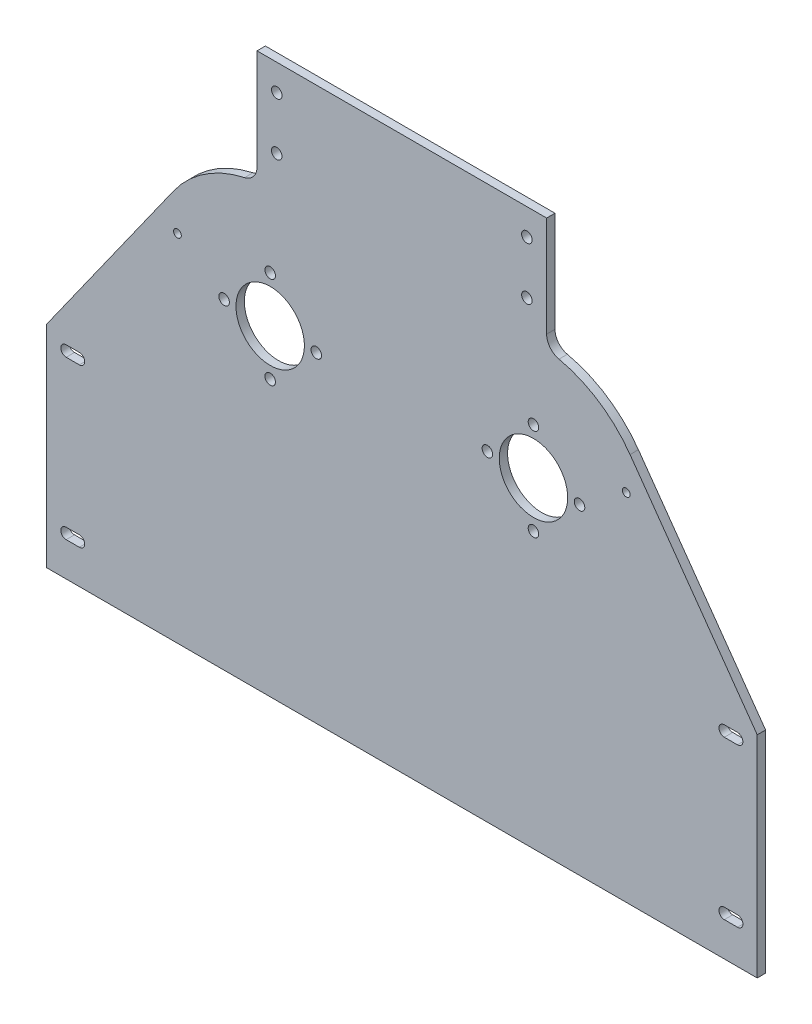
SolidWorks part; units mm, degrees
ref_plane "Front Plane" through (0, 0, 0) normal (0, 0, 1) x (1, 0, 0)
ref_plane "Top Plane" through (0, 0, 0) normal (0, 1, 0) x (1, 0, 0)
ref_plane "Right Plane" through (0, 0, 0) normal (1, 0, 0) x (0, 0, -1)
sketch "Sketch1" plane through (0, 0, 0) normal (0, 0, 1) x (1, 0, 0)
  line L1 (-100, -75) -> (100, -75)
  line L2 (-100, -75) -> (-100, 75)
  line L3 (-100, 75) -> (100, 75)
  line L4 (100, -75) -> (100, 75)
  line L5 (-100, -75) -> (100, 75) construction
  line L6 (-100, 75) -> (100, -75) construction
  line L8 (-47.5, 40) -> (47.5, 40) construction
  line L9 (0, 75) -> (0, -75) construction
  line L10 (-27, -44) -> (27, -44) construction
  line L11 (-27, -44) -> (-27, 28) construction
  line L12 (-27, 28) -> (27, 28) construction
  line L13 (27, -44) -> (27, 28) construction
  line L14 (-27, -44) -> (27, 28) construction
  line L15 (-27, 28) -> (27, -44) construction
  line L23 (-55, 70) -> (55, 70)
  line L24 (-55, 70) -> (-55, -70)
  line L25 (-55, -70) -> (55, -70)
  line L26 (55, 70) -> (55, -70)
  line L27 (-55, 70) -> (55, -70) construction
  line L28 (-55, -70) -> (55, 70) construction
  line L29 (-32.5, 70) -> (32.5, 70) construction
  line L30 (-32.5, 70) -> (-32.5, 55) construction
  line L31 (-32.5, 55) -> (32.5, 55) construction
  line L32 (32.5, 70) -> (32.5, 55) construction
  line L33 (-32.5, 70) -> (32.5, 55) construction
  line L34 (-32.5, 55) -> (32.5, 70) construction
  circle A2 centre (-47.5, 40) radius 2
  circle A3 centre (47.5, 40) radius 2
  circle A4 centre (-27, 28) radius 2 construction
  circle A5 centre (27, 28) radius 2 construction
  circle A6 centre (27, -44) radius 2 construction
  circle A7 centre (-27, -44) radius 2 construction
  circle A8 centre (-47.5, 60) radius 2
  circle A10 centre (47.5, 60) radius 2
  point P0 (0, 0)
  point P15 (0, 40)
  point P18 (0, -8)
  point P56 (0, 0)
  point P63 (0, 62.5)
  dimension "D3" = 4
  dimension "D4" = 20
  dimension "D5" = 4
  dimension "D8" = 4
  dimension "D1" = 150
  dimension "D2" = 200
  dimension "D6" = 72
  dimension "D7" = 54
  dimension "D14" = 30
  dimension "D15" = 140
  dimension "D16" = 110
  dimension "D17" = 95
  dimension "D18" = 12
  dimension "D19" = 15
  dimension "D20" = 65
extrude "Boss-Extrude1" add sketch "Sketch1" along normal blind 3.175 contours L23 L32 L31 L30 L24 L25 L26 A7 A6 A5 A4 A3 A2 region at (0, -0.1637, 0)
sketch "Sketch3" plane through (0, 0, 3.175) normal (0, 0, 1) x (1, 0, 0)
  line L0 (0, 31.3301) -> (0, 52.1198) construction
  line L1 (-50, -18) -> (-56.5118, 18.9303) construction
  line L2 (-50, -18) -> (50, -18) construction
  line L3 (-50, -18) -> (-87.5, -18) construction
  line L4 (-50, -18) -> (-85.2385, -5.1742) construction
  circle A0 centre (-50, -18) radius 45
  circle A1 centre (-50, -0.5) radius 2
  circle A2 centre (50, -18) radius 45
  circle A3 centre (-50, -18) radius 30
  circle A4 centre (50, -18) radius 30
  circle A5 centre (-47.5, 40) radius 2 construction
  circle A6 centre (-47.5, 40) radius 2
  circle A7 centre (47.5, 40) radius 2
  circle A8 centre (-32.5, -18) radius 2
  circle A9 centre (-50, -35.5) radius 2
  circle A10 centre (-67.5, -18) radius 2
  circle A11 centre (67.5, -18) radius 2
  circle A12 centre (50, -35.5) radius 2
  circle A13 centre (32.5, -18) radius 2
  circle A14 centre (50, -0.5) radius 2
  circle A15 centre (-50, -18) radius 13
  circle A16 centre (50, -18) radius 13
  circle A18 centre (-85.2385, -5.1742) radius 1.4732
  circle A19 centre (-50, -18) radius 37.5 construction
  circle A21 centre (85.2385, -5.1742) radius 1.4732
  point P28 (-50, -18)
  line M4 (55, -70) -> (55, 70)
  line M6 (-55, 70) -> (-55, -70)
  line M12 (-55, -70) -> (55, -70)
  circle M17 centre (-47.5, 40) radius 2
  circle M18 centre (47.5, 40) radius 2
  dimension "D1" = 100
  dimension "D2" = 90
  dimension "D3" = 58
  dimension "D4" = 60
  dimension "D5" = 4
  dimension "D7" = 35
  dimension "D8" = 26
  dimension "D9" = 7.5
  dimension "D6" = 4
  dimension "D11" = 80
  dimension "D12" = 20
extrude "Boss-Extrude3" add sketch "Sketch3" against normal up to surface (3.175 mm away) contours A3 M6 | A3 A0 M6 | A3 A0 M12 M6 M17 | A3 M6 | A4 M4 | A4 M4 | A4 A2 M4 | A4 A2 M4 M12 M18 region at (-20.6864, -50.7736, 3.175) region at (6.0296, -18, 3.175) region at (55.9798, -55.1509, 3.175) region at (-55.9798, 19.1509, 3.175) region at (-55.6423, 2.7902, 3.175) region at (-31.0835, 4.3824, 3.175) region at (55.6423, -38.7902, 3.175) region at (20.6946, -18, 3.175) up to face at (0, 0, 0)
sketch "Sketch4" plane through (0, 0, 3.175) normal (0, 0, 1) x (1, 0, 0)
  line L0 (-135, -95) -> (-60, -95) construction
  line L1 (-60, -60) -> (-66.1555, -60)
  line L2 (-60, -60) -> (-60, -130)
  line L3 (-60, -130) -> (-115, -130)
  line L4 (-135, -60) -> (-135, -130)
  line L5 (-60, -60) -> (-135, -130) construction
  line L6 (-60, -130) -> (-135, -60) construction
  line L11 (-135, -60) -> (-86.6945, 8.0483)
  line L12 (-66.1555, -60) -> (-135, -60)
  line L13 (-60, -130) -> (-115, -130) construction
  line L14 (-60, -130) -> (-60, -121.7157)
  line L19 (-115, -130) -> (-135, -130)
  line L21 (-125, -95) -> (-125, -60) construction
  line L22 (-122.5, -65) -> (-127.5, -65) construction
  line L23 (-122.5, -67.05) -> (-127.5, -67.05)
  line L24 (-122.5, -62.95) -> (-127.5, -62.95)
  line L25 (-122.5, -125) -> (-127.5, -125) construction
  line L26 (-122.5, -122.95) -> (-127.5, -122.95)
  line L27 (-122.5, -127.05) -> (-127.5, -127.05)
  line L28 (-60, -60) -> (0, -60)
  line L29 (-60, -60) -> (-60, -130)
  line L30 (-60, -130) -> (0, -130)
  line L31 (0, -60) -> (0, -130)
  line L32 (-60, -60) -> (0, -130) construction
  line L33 (-60, -130) -> (0, -60) construction
  line L34 (-135, -130) -> (0, -130)
  line L35 (-135, -130) -> (-135, -140)
  line L36 (-135, -140) -> (0, -140)
  line L37 (0, -130) -> (0, -140)
  line L38 (-135, -130) -> (0, -140) construction
  line L39 (-135, -140) -> (0, -130) construction
  arc A0 (-55, 26.7214) -> (-55, -62.7214) centre (-50, -18) ccw construction
  arc A1 (-86.6945, 8.0483) -> (-66.1555, -60) centre (-50, -18) ccw
  circle A2 centre (-125, -65) radius 2.05 construction
  arc A3 (-122.5, -67.05) -> (-122.5, -62.95) centre (-122.5, -65) ccw
  arc A4 (-127.5, -62.95) -> (-127.5, -67.05) centre (-127.5, -65) ccw
  arc A5 (-122.5, -122.95) -> (-122.5, -127.05) centre (-122.5, -125) cw
  arc A6 (-127.5, -127.05) -> (-127.5, -122.95) centre (-127.5, -125) cw
  point P4 (-97.5, -95)
  point P12 (-67.5, -135)
  point P26 (-30, -95)
  point P32 (-125, -65)
  point P40 (-125, -125)
  arc M12 (-55, 26.7214) -> (-55, -62.7214) centre (-50, -18) ccw
  line M18 (-55, -70) -> (55, -70)
  line M85 (-55, -62.7214) -> (-55, -70)
  dimension "D7" = 4.1
  dimension "D8" = 2.05
  dimension "D1" = 60
  dimension "D2" = 60
  dimension "D3" = 70
  dimension "D4" = 75
  dimension "D5" = 10
  dimension "D6" = 10
  dimension "D9" = 5
  dimension "D10" = 5
extrude "Boss-Extrude5" add sketch "Sketch4" against normal up to surface (3.175 mm away) contours L12 L4 A4 L24 A3 L23 L27 A6 L26 A5 M12 | L12 L11 M12 | L31 L2 L30 M18 M85 M12 | L29 L28 L31 L30 | L35 L34 L37 L36 region at (-97.1847, -95.0416, 3.175) region at (-103.3765, -42.7351, 3.175) region at (-30.2897, -99.6442, 3.175) up to face at (59, -18, 0)
mirror "Mirror2" about plane through (0, 0, 0) normal (1, 0, 0) of "Boss-Extrude5"
fillet "Fillet1" radius 6 2 edges at (55, 26.7214, 1.5875) (-55, 26.7214, 1.5875)
ref_plane "Plane1" through (-55, -6, 3.175) normal (0, -1, 0) x (-1, 0, 0)
sketch "Sketch6" plane through (0, 0, 3.175) normal (0, 0, 1) x (1, 0, 0)
  circle A0 centre (32.5, -18) radius 2 construction
  circle A1 centre (50, -0.5) radius 2 construction
  circle A2 centre (67.5, -18) radius 2 construction
  circle A3 centre (50, -18) radius 13 construction
  circle A4 centre (50, -35.5) radius 2 construction
  circle A5 centre (-50, -18) radius 13 construction
  circle A6 centre (-67.5, -18) radius 2 construction
  circle A7 centre (-50, -35.5) radius 2 construction
  circle A8 centre (-32.5, -18) radius 2 construction
  circle A9 centre (-50, -0.5) radius 2 construction
  circle A10 centre (32.5, -18) radius 2
  circle A11 centre (50, -0.5) radius 2
  circle A12 centre (67.5, -18) radius 2
  circle A13 centre (50, -18) radius 13
  circle A14 centre (50, -35.5) radius 2
  circle A15 centre (-50, -18) radius 13
  circle A16 centre (-67.5, -18) radius 2
  circle A17 centre (-50, -35.5) radius 2
  circle A18 centre (-32.5, -18) radius 2
  circle A19 centre (-50, -0.5) radius 2
extrude "Cut-Extrude1" cut sketch "Sketch6" against normal blind 10
